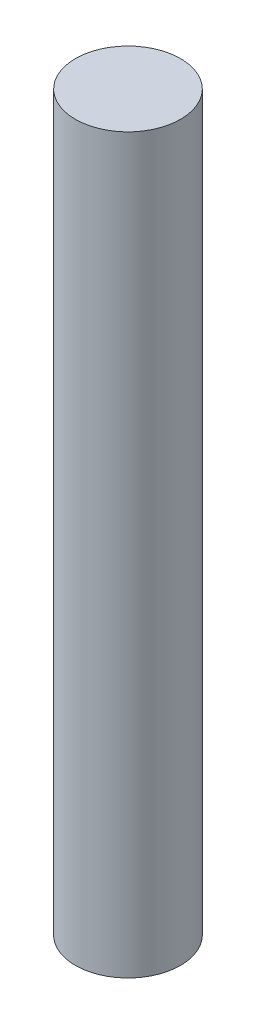
SolidWorks part; units mm, degrees
ref_plane "Front Plane" through (0, 0, 0) normal (0, 0, 1) x (1, 0, 0)
ref_plane "Top Plane" through (0, 0, 0) normal (0, 1, 0) x (1, 0, 0)
ref_plane "Right Plane" through (0, 0, 0) normal (1, 0, 0) x (0, 0, -1)
sketch "Sketch1" plane through (0, 0, 0) normal (0, 1, 0) x (1, 0, 0)
  circle A0 centre (0, 0) radius 38.1
  dimension "D1" = 76.2
extrude "Boss-Extrude1" add sketch "Sketch1" along normal blind 530.86
equation "\"Motor_Length\" = 20.90in"
equation "\"Motor_OD\" = 3in"
equation "\"D1@Sketch1\"=\"Motor_OD\""
equation "\"D1@Boss-Extrude1\"=\"Motor_Length\""
